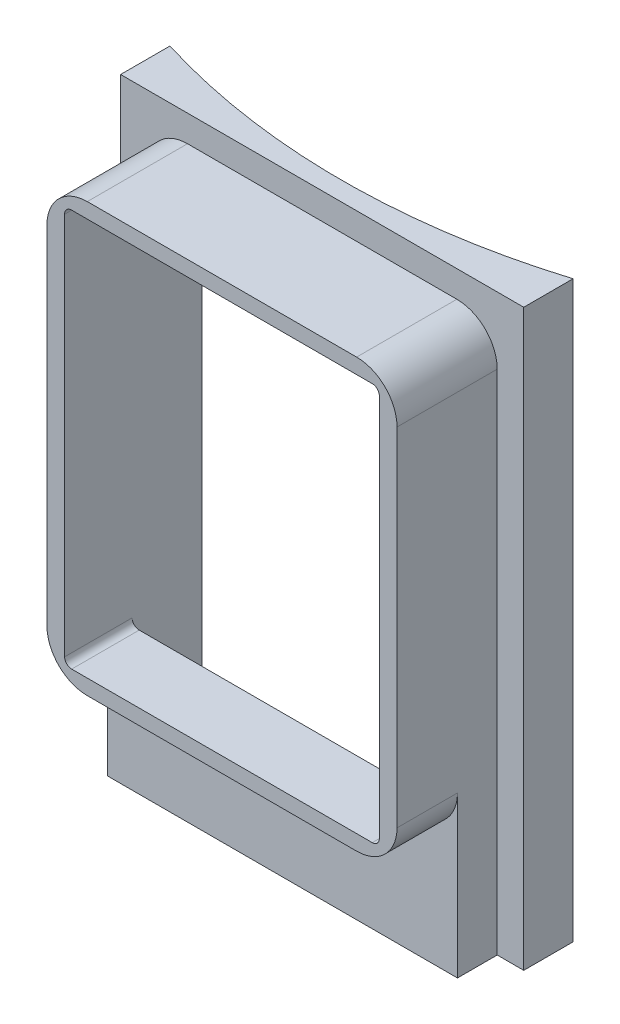
SolidWorks part; units mm, degrees
ref_plane "Front Plane" through (0, 0, 0) normal (0, 0, 1) x (1, 0, 0)
ref_plane "Top Plane" through (0, 0, 0) normal (0, 1, 0) x (1, 0, 0)
ref_plane "Right Plane" through (0, 0, 0) normal (1, 0, 0) x (0, 0, -1)
sketch "Sketch1" plane through (0, 0, 0) normal (0, 0, 1) x (1, 0, 0)
  line L1 (-46.99, 86.36) -> (97.79, 86.36)
  line L2 (-46.99, 86.36) -> (-46.99, -119.888)
  line L3 (-46.99, -119.888) -> (97.79, -119.888)
  line L4 (97.79, 86.36) -> (97.79, -119.888)
  dimension "D1" = 144.78
  dimension "D2" = 206.248
extrude "Extrude1" add sketch "Sketch1" along normal blind 252.4252
sketch "Sketch2" plane through (0, 86.36, 0) normal (0, 1, 0) x (-1, 0, 0)
  line L0 (-97.79, 0) -> (46.99, 0) construction
  circle A1 centre (-25.4, 0) radius 245.618
sketch "Sketch7" plane through (0, 0, 252.4252) normal (0, 0, 1) x (1, 0, 0)
  line L0 (-46.99, 86.36) -> (-46.99, -119.888) construction
  line L1 (-37.465, 76.835) -> (88.265, 76.835)
  line L2 (-37.465, 76.835) -> (-37.465, -119.888)
  line L3 (-37.465, -119.888) -> (88.265, -119.888)
  line L4 (88.265, 76.835) -> (88.265, -119.888)
  line L5 (97.79, -119.888) -> (97.79, 86.36) construction
  line L6 (97.79, 86.36) -> (-46.99, 86.36) construction
  line L7 (-46.99, -119.888) -> (97.79, -119.888) construction
  point P8 (25.4, 76.835)
  point P9 (0, 0)
  dimension "D1" = 9.525
  dimension "D2" = 9.525
  dimension "D3" = 9.525
extrude "Extrude5" add sketch "Sketch7" along normal blind 35.9842
sketch "Sketch4" plane through (0, 0, 252.4252) normal (0, 0, 1) x (1, 0, 0)
  line L0 (97.79, 86.36) -> (-46.99, 86.36) construction
  line L1 (-31.115, 71.374) -> (81.915, 71.374)
  line L2 (-31.115, 71.374) -> (-31.115, -71.374)
  line L3 (-31.115, -71.374) -> (81.915, -71.374)
  line L4 (81.915, 71.374) -> (81.915, -71.374)
  line L5 (88.265, 76.835) -> (-37.465, 76.835) construction
  line L6 (88.265, 76.835) -> (-37.465, 76.835) construction
  point P4 (25.4, 71.374)
  point P5 (25.4, 86.36)
  point P6 (25.4, 76.835)
  dimension "D1" = 5.461
  dimension "D2" = 142.748
extrude "Extrude2" cut sketch "Sketch4" against normal blind 273.8502 and the other way blind 42.08
sketch "Sketch10" plane through (0, 0, 0) normal (0, 0, -1) x (-1, 0, 0)
  line L0 (46.99, -119.888) -> (-97.79, -119.888) construction
  line L1 (-81.915, 71.374) -> (31.115, 71.374)
  line L2 (-81.915, 71.374) -> (-81.915, 74.295)
  line L3 (-81.915, 74.295) -> (31.115, 74.295)
  line L4 (31.115, 71.374) -> (31.115, 74.295)
  line L5 (-81.915, -71.374) -> (31.115, -71.374)
  line L6 (-81.915, -71.374) -> (-81.915, -117.348)
  line L7 (-81.915, -117.348) -> (31.115, -117.348)
  line L8 (31.115, -71.374) -> (31.115, -117.348)
  dimension "D1" = 2.54
extrude "Extrude8" cut sketch "Sketch10" against normal blind 264.16
sketch "Sketch11" plane through (0, 0, 264.16) normal (0, 0, -1) x (-1, 0, 0)
  line L0 (-81.915, 71.374) -> (31.115, 71.374) construction
  line L1 (31.115, 74.295) -> (-81.915, 74.295)
  line L2 (31.115, 74.295) -> (31.115, 71.374)
  line L3 (31.115, 71.374) -> (-81.915, 71.374)
  line L4 (-81.915, 74.295) -> (-81.915, 71.374)
extrude "Extrude9" cut sketch "Sketch11" against normal blind 21.59
fillet "Fillet1" radius 2.54 8 edges at (81.915, -71.374, 276.2847) (-31.115, -71.374, 276.2847) (81.915, 71.374, 287.0797) (-31.115, 71.374, 287.0797) (81.915, -117.348, 132.08) (-31.115, -117.348, 132.08) (-31.115, 74.295, 142.875) (81.915, 74.295, 142.875)
extrude "Extrude4" cut sketch "Sketch2" against normal blind 230
sketch "Sketch12" plane through (0, 0, 288.4094) normal (0, 0, 1) x (1, 0, 0)
  line L0 (88.265, -119.888) -> (88.265, 76.835) construction
  line L1 (-37.465, -119.888) -> (88.265, -119.888)
  line L2 (-37.465, -119.888) -> (-37.465, -76.835)
  line L3 (-37.465, -76.835) -> (88.265, -76.835)
  line L4 (88.265, -119.888) -> (88.265, -76.835)
  dimension "D1" = 5.461
extrude "Extrude10" cut sketch "Sketch12" against normal blind 21.7094
fillet "Fillet4" radius 14.5 4 edges at (88.265, 76.835, 270.4173) (-37.465, -76.835, 277.5547) (88.265, -76.835, 277.5547) (-37.465, 76.835, 270.4173)
